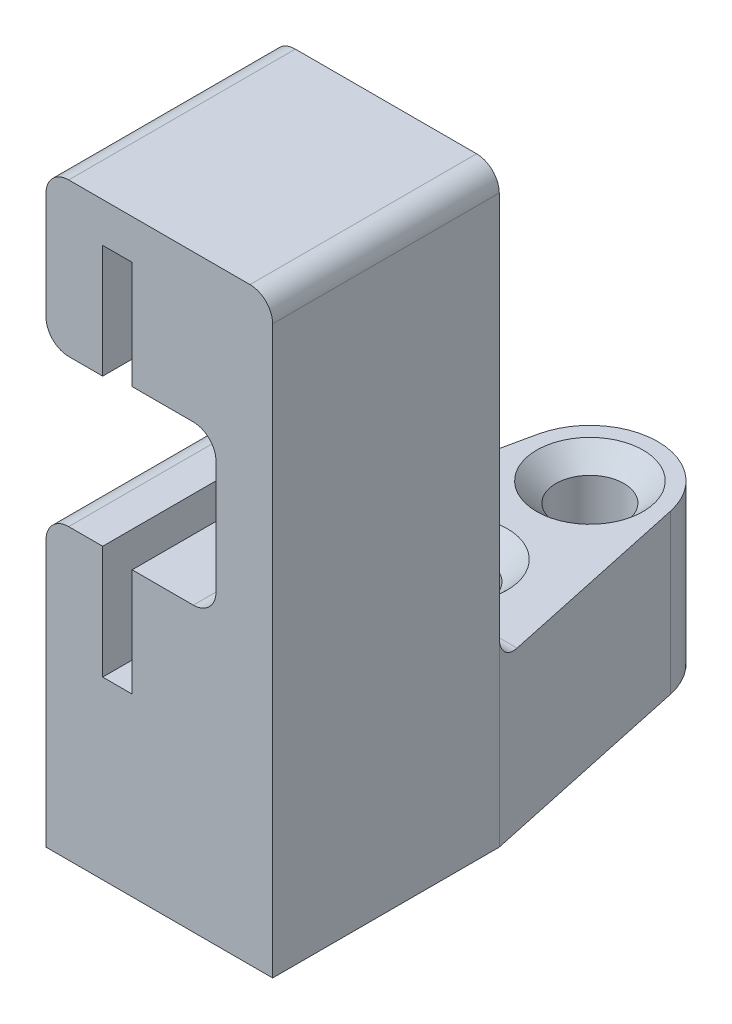
SolidWorks part; units mm, degrees
ref_plane "Front Plane" through (0, 0, 0) normal (0, 0, 1) x (1, 0, 0)
ref_plane "Top Plane" through (0, 0, 0) normal (0, 1, 0) x (1, 0, 0)
ref_plane "Right Plane" through (0, 0, 0) normal (1, 0, 0) x (0, 0, -1)
sketch "Sketch1" plane through (0, 0, 0) normal (0, 0, 1) x (1, 0, 0)
  line L6 (-5, 0) -> (5, 0)
  line L7 (5, 0) -> (5, 26)
  line L8 (5, 26) -> (-5, 26)
  line L9 (-5, 26) -> (-5, 19.25)
  line L10 (-5, 19.25) -> (-2.5, 19.25)
  line L11 (-2.5, 19.25) -> (-2.5, 24.25)
  line L12 (-2.5, 24.25) -> (-1.2, 24.25)
  line L13 (-1.2, 24.25) -> (-1.2, 19.5)
  line L14 (-1.2, 19.5) -> (2.5, 19.5)
  line L15 (2.5, 19.5) -> (2.5, 12.5)
  line L16 (2.5, 12.5) -> (-1.2, 12.5)
  line L17 (-1.2, 12.5) -> (-1.2, 7.75)
  line L18 (-1.2, 7.75) -> (-2.5, 7.75)
  line L19 (-2.5, 7.75) -> (-2.5, 12.75)
  line L20 (-2.5, 12.75) -> (-5, 12.75)
  line L21 (-5, 12.75) -> (-5, 0)
  line L22 (2.5, 16) -> (-0.044, 16) construction
  point P4 (0, 0)
  dimension "D1" = 16.5
  dimension "D2" = 10
  dimension "D3" = 1.3
  dimension "D4" = 2.5
  dimension "D5" = 2.5
  dimension "D6" = 7
  dimension "D7" = 6.5
  dimension "D8" = 10
  dimension "D9" = 16
extrude "Boss-Extrude1" add sketch "Sketch1" along normal mid plane 10
sketch "Sketch2" plane through (0, 0, 0) normal (0, 1, 0) x (1, 0, 0)
  line L0 (-5, -5) -> (0.7077, -13.2718) construction
  line L1 (7.4049, -8.9008) -> (5, -5) construction
  line L2 (5, -5) -> (-5, -5) construction
  line L3 (-5, -5) -> (-5, 5) construction
  line L4 (-5, 0) -> (5, 0) construction
  line L5 (5, -5) -> (5, 5) construction
  line L9 (4, -11) -> (1.4443, -7.2962) construction
  line L10 (5, 5) -> (2.9332, 14.6296)
  line L11 (-2.9332, 14.6296) -> (-5, 5)
  line L12 (-5, 5) -> (5, 5)
  arc A0 (0.7077, -13.2718) -> (7.4049, -8.9008) centre (4, -11) ccw construction
  circle A2 centre (4, -11) radius 1 construction
  circle A3 centre (1.4443, -7.2962) radius 1 construction
  arc A4 (2.9332, 14.6296) -> (-2.9332, 14.6296) centre (0, 14) ccw
  dimension "D1" = 6
  dimension "D3" = 4
  dimension "D4" = 2
  dimension "D9" = 3
  dimension "D2" = 9
  dimension "D5" = 4.5
  dimension "D7" = 9
extrude "Boss-Extrude2" add sketch "Sketch2" along normal blind 7
hole_wizard "Ø3.0mm Dowel Hole1" positions "Sketch3" profile "Sketch5" hole size "Ø3.0" standard "ANSI Metric" end condition through all
sketch "Sketch3" plane through (0, 7, 0) normal (0, 1, 0) x (1, 0, 0)
  arc A0 (2.9332, 14.6296) -> (-2.9332, 14.6296) centre (0, 14) ccw construction
  point P0 (0, 14)
  point P2 (0, 8)
  dimension "D1" = 6
sketch "Sketch5" plane through (0, 7, -14) normal (1, 0, 0) x (0, 0, 1)
  line L0 (0, 0) -> (0, 7)
  line L1 (0, 7) -> (1.5, 7)
  line L2 (1.5, 7) -> (1.5, 0.85)
  line L3 (1.5, 0.85) -> (2.35, 0)
  line L5 (2.35, 0) -> (0, 0)
  line L6 (-1.5, 0.85) -> (-2.35, 0) construction
  line L11 (0, -6.35) -> (0, 107.95) construction
  dimension "Thru Hole Dia." = 3
  dimension "Thru Hole Depth" = 7
  dimension "Near C'Sink Dia." = 4.7
  dimension "Near C'Sink Angle" = 90
fillet "Fillet1" radius 1 7 edges at (2.5, 19.5, 0) (-5, 19.25, 0) (-5, 12.75, 0) (2.5, 12.5, 0) (5, 26, 0) (-5, 26, 0) (0, 7, -5)
